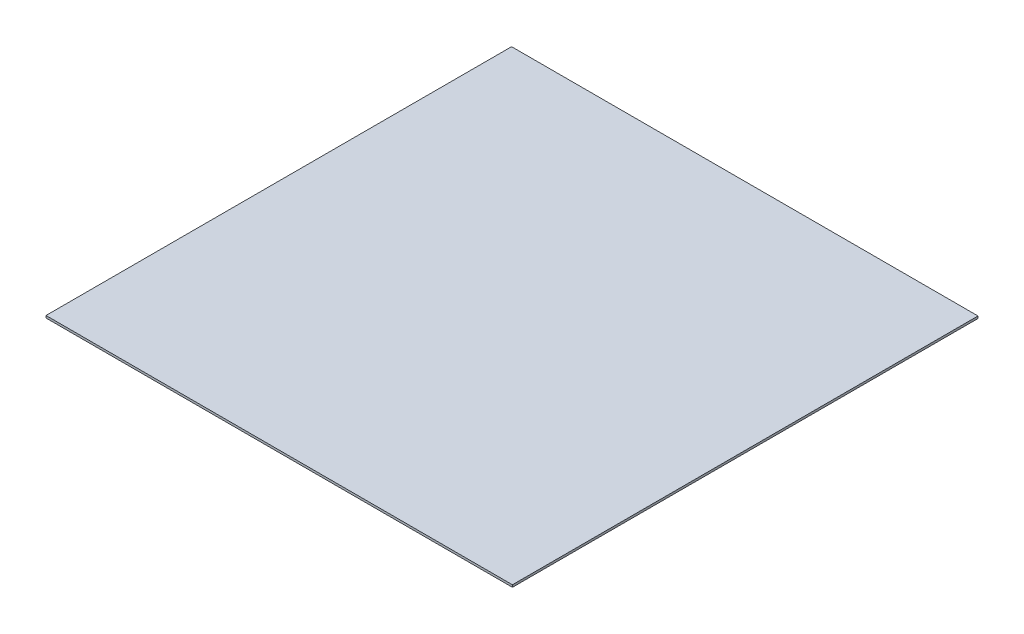
SolidWorks part; units mm, degrees
ref_plane "Front Plane" through (0, 0, 0) normal (0, 0, 1) x (1, 0, 0)
ref_plane "Top Plane" through (0, 0, 0) normal (0, 1, 0) x (1, 0, 0)
ref_plane "Right Plane" through (0, 0, 0) normal (1, 0, 0) x (0, 0, -1)
sketch "Sketch1" plane through (0, 0, 0) normal (0, 1, 0) x (1, 0, 0)
  line L1 (254, -254) -> (-254, -254)
  line L2 (254, -254) -> (254, 254)
  line L3 (254, 254) -> (-254, 254)
  line L4 (-254, -254) -> (-254, 254)
  line L5 (0, 254) -> (0, -254) construction
  line L6 (254, 0) -> (-254, 0) construction
  point P0 (0, 0)
  dimension "D1" = 508
  dimension "D2" = 508
extrude "Boss-Extrude1" add sketch "Sketch1" along normal blind 3
sketch "Sketch2" plane through (0, 3, 0) normal (0, 1, 0) x (1, 0, 0)
  line L1 (314.275, -313.705) -> (-314.275, -313.705)
  line L2 (314.275, -313.705) -> (314.275, 313.705)
  line L3 (314.275, 313.705) -> (-314.275, 313.705)
  line L4 (-314.275, -313.705) -> (-314.275, 313.705)
  line L5 (0, 313.705) -> (0, -313.705) construction
  line L6 (314.275, 0) -> (-314.275, 0) construction
  point P0 (0, 0)
  dimension "D1" = 628.55
  dimension "D2" = 627.41
sketch "Sketch5" plane through (0, 3, 0) normal (0, 1, 0) x (1, 0, 0)
  line L0 (-314.275, -313.705) -> (-314.275, 313.705) construction
  line L1 (-314.275, 254) -> (314.275, 254)
  line L2 (-314.275, 254) -> (-314.275, 313.705)
  line L3 (-314.275, 313.705) -> (314.275, 313.705)
  line L4 (314.275, 254) -> (314.275, 313.705)
  line L6 (-314.275, 254) -> (-254, 254)
  line L7 (-314.275, 254) -> (-314.275, -254)
  line L8 (-314.275, -254) -> (-254, -254)
  line L9 (-254, 254) -> (-254, -254)
  line L10 (-314.275, -254) -> (314.275, -254)
  line L11 (-314.275, -254) -> (-314.275, -313.705)
  line L12 (-314.275, -313.705) -> (314.275, -313.705)
  line L13 (314.275, -254) -> (314.275, -313.705)
  line L14 (314.275, -254) -> (254, -254)
  line L15 (314.275, -254) -> (314.275, 254)
  line L16 (314.275, 254) -> (254, 254)
  line L17 (254, -254) -> (254, 254)
  point P17 (0, 0)
extrude "Boss-Extrude2" add sketch "Sketch5" against normal blind 3 contours L7 L6 L9 L8 | L11 L10 L13 L12 | L15 L14 L17 L16 | L2 L1 L4 L3
ref_plane "Plane1" through (0, 0, 253.995) normal (0, 0, 1) x (1, 0, 0)
ref_plane "Plane2" through (0, 0, -253.995) normal (0, 0, -1) x (-1, 0, 0)
ref_plane "Plane3" through (254.275, 0, 0) normal (1, 0, 0) x (0, 0, -1)
ref_plane "Plane4" through (-254.275, 0, 0) normal (-1, 0, 0) x (0, 0, 1)
